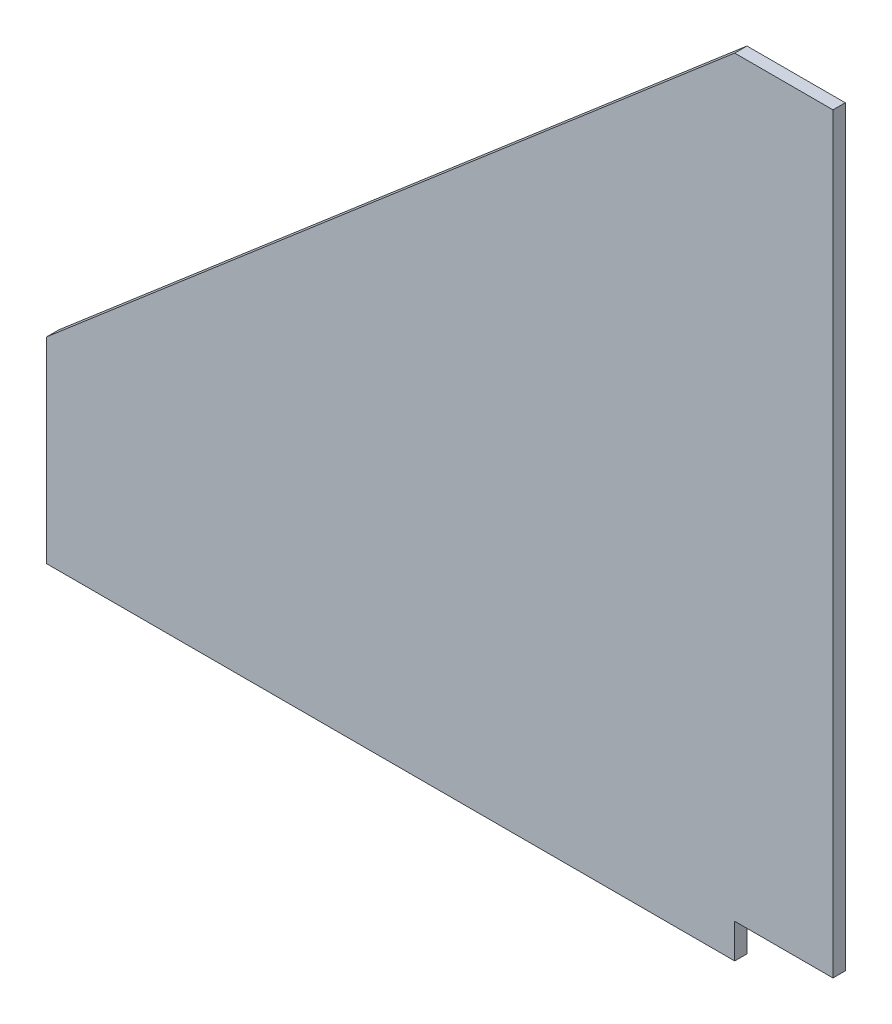
SolidWorks part; units mm, degrees
material "A-Glass Fiber"
ref_plane "Front Plane" through (0, 0, 0) normal (0, 0, 1) x (1, 0, 0)
ref_plane "Top Plane" through (0, 0, 0) normal (0, 1, 0) x (1, 0, 0)
ref_plane "Right Plane" through (0, 0, 0) normal (1, 0, 0) x (0, 0, -1)
sketch "Sketch1" plane through (0, 0, 0) normal (0, 0, 1) x (1, 0, 0)
  line L0 (0, 0) -> (0, 194.31)
  line L1 (0, 194.31) -> (-25.4, 194.31)
  line L3 (-203.2, -8.89) -> (-25.4, -8.89)
  line L4 (-25.4, -8.89) -> (-25.4, 0)
  line L5 (-25.4, 0) -> (0, 0)
  line L6 (-203.2, -8.89) -> (-203.2, 41.91)
  line L7 (-203.2, 41.91) -> (-25.4, 194.31)
  dimension "D1" = 194.31
  dimension "D2" = 177.8
  dimension "D3" = 25.4
  dimension "D4" = 203.2
  dimension "D5" = 25.4
  dimension "D6" = 50.8
extrude "Boss-Extrude1" add sketch "Sketch1" along normal blind 3.175
